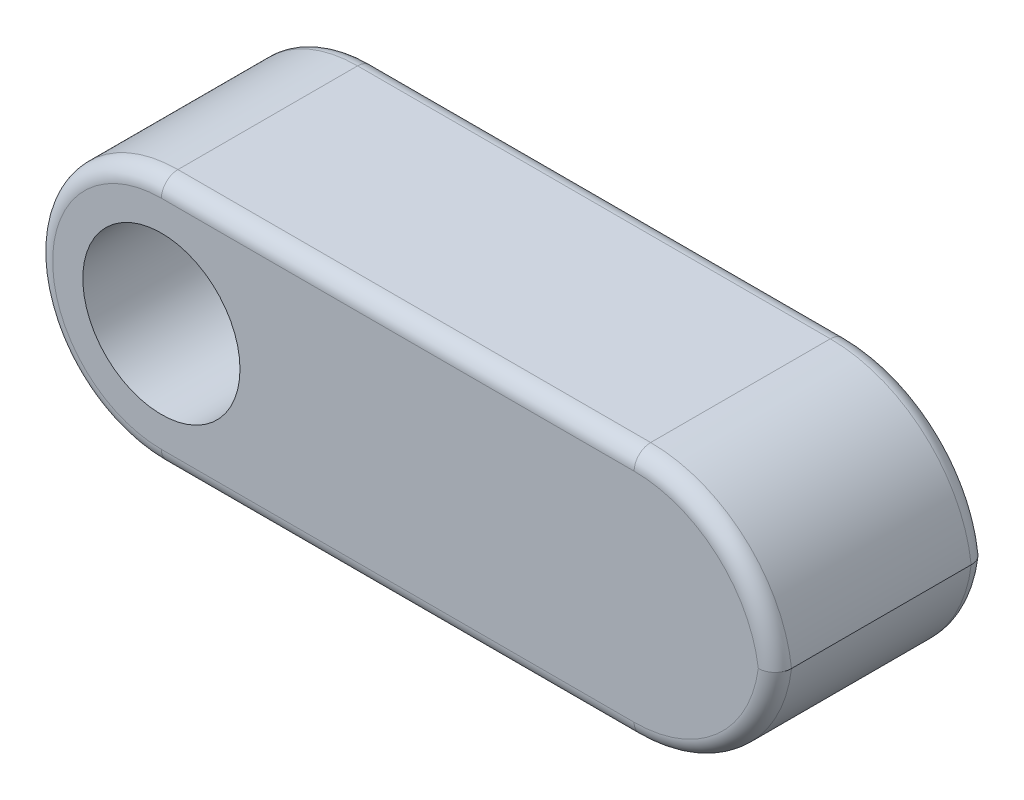
SolidWorks part; units mm, degrees
ref_plane "Front Plane" through (0, 0, 0) normal (0, 0, 1) x (1, 0, 0)
ref_plane "Top Plane" through (0, 0, 0) normal (0, 1, 0) x (1, 0, 0)
ref_plane "Right Plane" through (0, 0, 0) normal (1, 0, 0) x (0, 0, -1)
sketch "Sketch1" plane through (0, 0, 0) normal (0, 0, 1) x (1, 0, 0)
  line L0 (0, 6.731) -> (33.02, 6.731)
  line L1 (0, -6.731) -> (33.02, -6.731)
  line L2 (33.02, 6.731) -> (33.02, -6.731)
  circle A0 centre (0, 0) radius 4.2227
  circle A1 centre (0, 0) radius 6.731
  dimension "D1" = 8.4455
  dimension "D2" = 13.462
  dimension "D3" = 33.02
extrude "Boss-Extrude1" add sketch "Sketch1" along normal blind 11.43 contours A1 L1 L2 L0 | A1 A0 region at (19.1126, 0, 0) region at (4.6249, 4.6249, 0)
fillet "Front Fillet" radius 7.62 2 edges at (33.02, -6.731, 5.715) (33.02, 6.731, 5.715)
fillet "Side Fillet" radius 0.889 10 edges at (12.7, 6.731, 0) (-6.731, 0, 0) (12.7, -6.731, 0) (30.4641, -4.8048, 0) (30.4641, 4.8048, 0) (-6.731, 0, 11.43) (12.7, 6.731, 11.43) (30.4641, 4.8048, 11.43) (30.4641, -4.8048, 11.43) (12.7, -6.731, 11.43)
equation "\"UpperAxleDiameter\"=0.3325"
equation "\"D1@Sketch1\"=\"UpperAxleDiameter\""
equation "\"toeLength\"=1.3"
equation "\"D3@Sketch1\"=\"toeLength\""
equation "\"toeWidth\"= 0.5"
